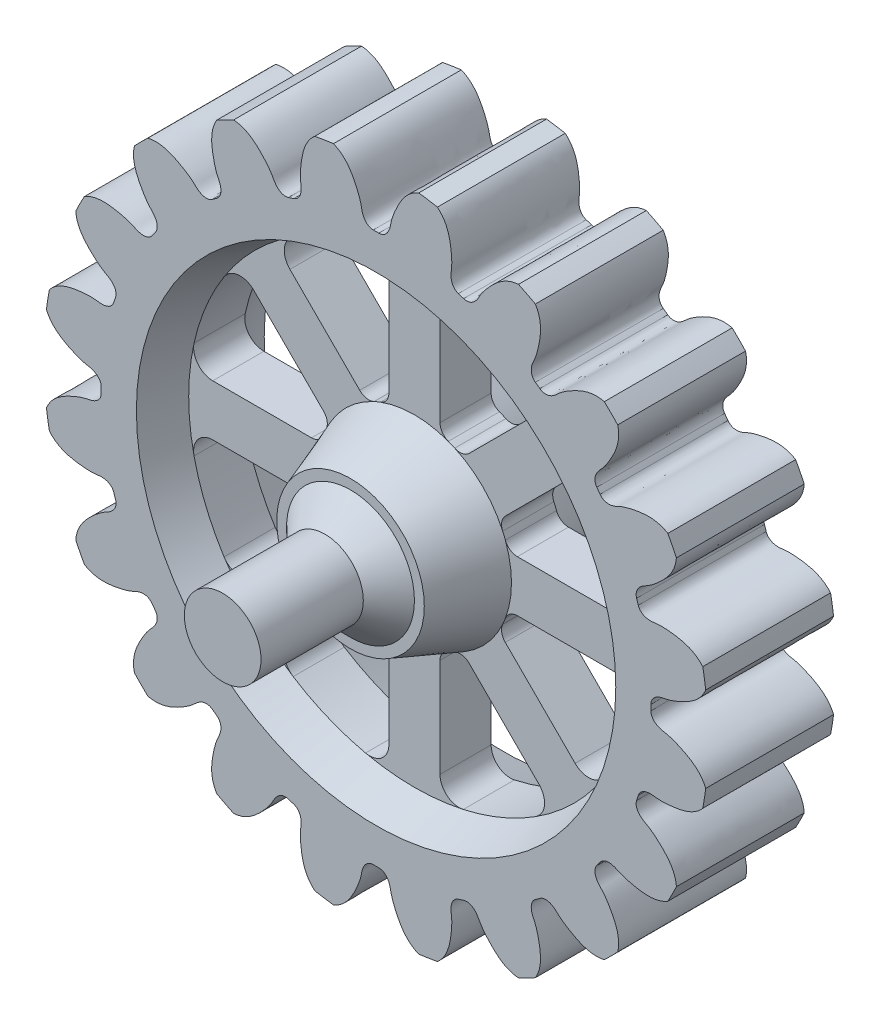
SolidWorks part; units mm, degrees
ref_plane "Front Plane" through (0, 0, 0) normal (0, 0, 1) x (1, 0, 0)
ref_plane "Top Plane" through (0, 0, 0) normal (0, 1, 0) x (1, 0, 0)
ref_plane "Right Plane" through (0, 0, 0) normal (1, 0, 0) x (0, 0, -1)
ref_axis "Axis1" through (0, 0, -88.99) along (0, 0, 1)
sketch "Gear-BaseSketch" plane through (0, 0, 0) normal (0, 0, 1) x (1, 0, 0)
  circle A0 centre (0, 0) radius 52
  dimension "D1" = 104
extrude "GearModule" add sketch "Gear-BaseSketch" along normal mid plane 20
sketch "Tooth-Sketch; Backlash: 0,0000mm" plane through (0, 0, 0) normal (0, 0, 1) x (1, 0, 0)
  line L0 (0, 0) -> (0, 67.6579) construction
  arc A0 (-6.8515, 51.6426) -> (6.8515, 51.6426) centre (0, 0) cw
  arc A1 (-0.4313, 42.9978) -> (0.4313, 42.9978) centre (0, 0) cw
  spline S0 degree 3 poles (-6.8515, 51.6426) (-4.8458, 50.9021) (-3.4055, 48.5063) (-2.4064, 45.8957) (-2.2675, 45.0318) (-2.2451, 44.9176) (-2.2051, 44.7342) (-2.1379, 44.4865) (-2.0249, 44.1806) (-1.8786, 43.8874) (-1.6839, 43.6026) (-1.4152, 43.3302) (-1.0028, 43.0725) (-0.6435, 42.9987) (-0.4313, 42.9978) knots 0 0 0 0 0.514022 0.725405 0.73589 0.746181 0.756292 0.785707 0.814222 0.842705 0.872478 0.90542 0.943594 1 1 1 1
  spline S1 degree 3 poles (6.8515, 51.6426) (4.8458, 50.9021) (3.4055, 48.5063) (2.4064, 45.8957) (2.2675, 45.0318) (2.2451, 44.9176) (2.2051, 44.7342) (2.1379, 44.4865) (2.0249, 44.1806) (1.8786, 43.8874) (1.6839, 43.6026) (1.4152, 43.3302) (1.0028, 43.0725) (0.6435, 42.9987) (0.4313, 42.9978) knots 0 0 0 0 0.514022 0.725405 0.73589 0.746181 0.756292 0.785707 0.814222 0.842705 0.872478 0.90542 0.943594 1 1 1 1
  point P3 (0, 0)
  point P5 (6.8515, 51.6426)
  point P6 (4.245, 49.6084)
  point P7 (0, 0)
  point P8 (4.1807, 49.7847)
  point P10 (3.0333, 47.4176)
  point P11 (0, 0)
  point P12 (0, 0)
  point P52 (6.2069, 51.724)
  point P53 (4.7817, 50.8545)
extrude "Tooth-Cut" cut sketch "Tooth-Sketch; Backlash: 0,0000mm" against normal through all and the other way through all
pattern_circular "Tooth Pattern 20" count 20 over 360 about axis through (0, 0, -88.99) along (0, 0, 1) of "Tooth-Cut"
sketch "Sketch4" plane through (0, 0, 10) normal (0, 0, 1) x (1, 0, 0)
  circle A0 centre (0, 0) radius 37.5
  circle A1 centre (0, 0) radius 13
  dimension "D1" = 75
  dimension "D2" = 26
extrude "Cut-Extrude2" cut sketch "Sketch4" against normal blind 6 draft 20
mirror "Mirror1" about plane through (0, 0, 0) normal (0, 0, 1) of "Cut-Extrude2"
sketch "Sketch5" plane through (0, 0, 10) normal (0, 0, 1) x (1, 0, 0)
  circle A0 centre (0, 0) radius 13
extrude "Boss-Extrude2" add sketch "Sketch5" along normal blind 4 draft 20
mirror "Mirror2" about plane through (0, 0, 0) normal (0, 0, 1) of "Boss-Extrude2"
sketch "Sketch6" plane through (0, 0, 0) normal (0, 0, 1) x (1, 0, 0)
  line L1 (-2, 8.5) -> (2, 8.5)
  line L2 (-2, 8.5) -> (-2, 6.7082)
  line L4 (2, 8.5) -> (2, 6.7082)
  arc A0 (-2, 6.7082) -> (2, 6.7082) centre (0, 0) ccw
  dimension "D1" = 14
  dimension "D4" = 4
  dimension "D5" = 2
extrude "Cut-Extrude3" cut sketch "Sketch6" against normal mid plane 34
sketch "Sketch7" plane through (0, 0, 0) normal (0, 0, 1) x (1, 0, 0)
  line L4 (-8.5576, 14.2145) -> (-19.48, 25.1369)
  line L5 (-4, 16.1023) -> (-4, 31.5489)
  arc A0 (-5.3017, 14.2282) -> (-6.312, 13.8097) centre (0, 0) ccw
  arc A1 (-7.6498, 34.4777) -> (-18.9702, 29.7887) centre (0, 0) ccw
  arc A2 (-19.48, 25.1369) -> (-18.9702, 29.7887) centre (-17.3587, 27.2582) cw
  arc A3 (-4, 31.5489) -> (-7.6498, 34.4777) centre (-7, 31.5489) ccw
  arc A4 (-4, 16.1023) -> (-5.3017, 14.2282) centre (-6, 16.1023) cw
  arc A5 (-8.5576, 14.2145) -> (-6.312, 13.8097) centre (-7.1434, 15.6287) ccw
  dimension "D1" = 3
  dimension "D2" = 2
extrude "Cut-Extrude4" cut sketch "Sketch7" against normal mid plane 34
pattern_circular "CirPattern2" count 8 over 360 about axis through (0, 0, 14) along (0, 0, 1) of "Cut-Extrude4"
sketch "Sketch8" plane through (0, 0, 14) normal (0, 0, 1) x (1, 0, 0)
  circle A0 centre (0, 0) radius 10
  dimension "D1" = 20
extrude "Boss-Extrude3" add sketch "Sketch8" along normal blind 20
sketch "Sketch9" plane through (0, 0, 34) normal (0, 0, 1) x (1, 0, 0)
  circle A0 centre (0, 0) radius 6
  circle A1 centre (0, 0) radius 13.045
  dimension "D1" = 12
extrude "Cut-Extrude5" cut sketch "Sketch9" against normal blind 15
chamfer "Chamfer1" distance 5 angle 45 1 edges at (10, 0, 19)
scale "Scale1" scale about centroid uniform scaling yes scale factor 0.7
